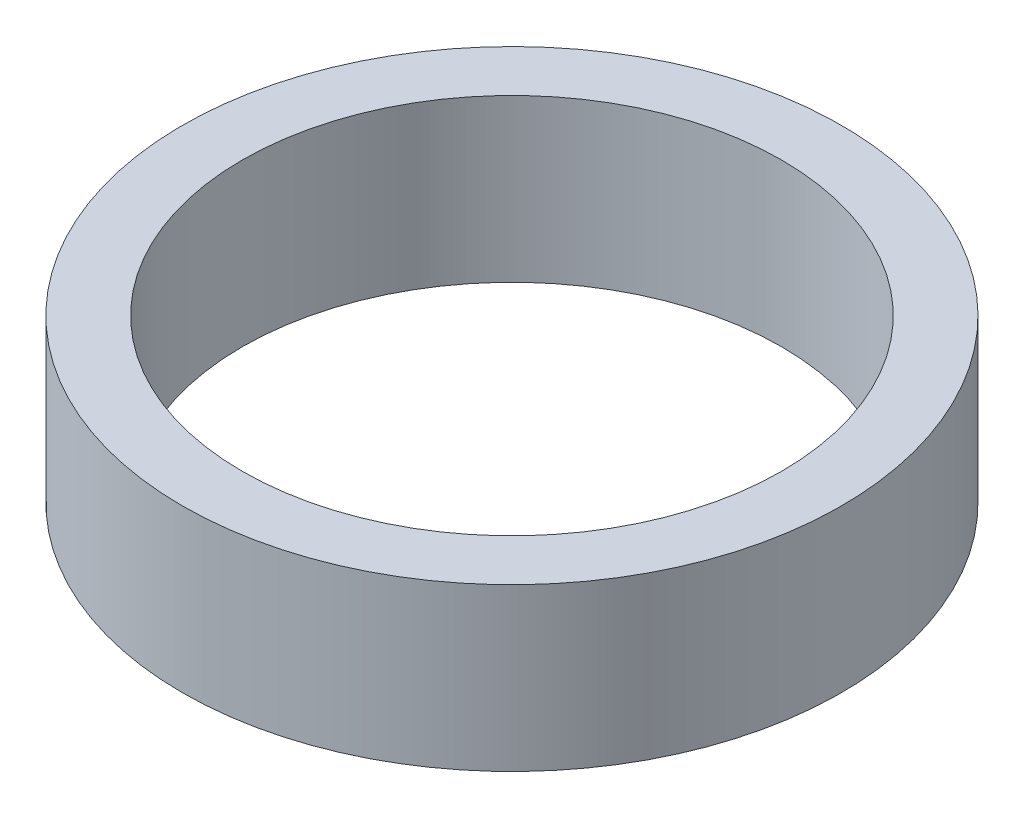
SolidWorks part; units mm, degrees
ref_plane "Front Plane" through (0, 0, 0) normal (0, 0, 1) x (1, 0, 0)
ref_plane "Top Plane" through (0, 0, 0) normal (0, 1, 0) x (1, 0, 0)
ref_plane "Right Plane" through (0, 0, 0) normal (1, 0, 0) x (0, 0, -1)
sketch "Sketch1" plane through (0, 0, 0) normal (0, 1, 0) x (1, 0, 0)
  circle A0 centre (0, 0) radius 55
  dimension "FLANGE_OD" = 110
extrude "Boss-Extrude1" add sketch "Sketch1" along normal blind 27
sketch "Sketch2" plane through (0, 0, 0) normal (0, 1, 0) x (1, 0, 0)
  circle A0 centre (0, 0) radius 45
  dimension "BORE_D" = 90
extrude "Cut-Extrude1" cut sketch "Sketch2" along normal through all
sketch "Sketch3" plane through (0, 27, 0) normal (0, 1, 0) x (1, 0, 0)
  circle A0 centre (0, 0) radius 23.8545 construction
  circle A1 centre (-23.8545, 0) radius 1.5114
  dimension "BOLT_D" = 3.0228
  dimension "BOLT_PCD" = 47.709
extrude "Cut-Extrude2" cut sketch "Sketch3" against normal blind 26.0978 rebuild error yes
pattern_circular "CirPattern1" count 8 over 360 rebuild error yes
